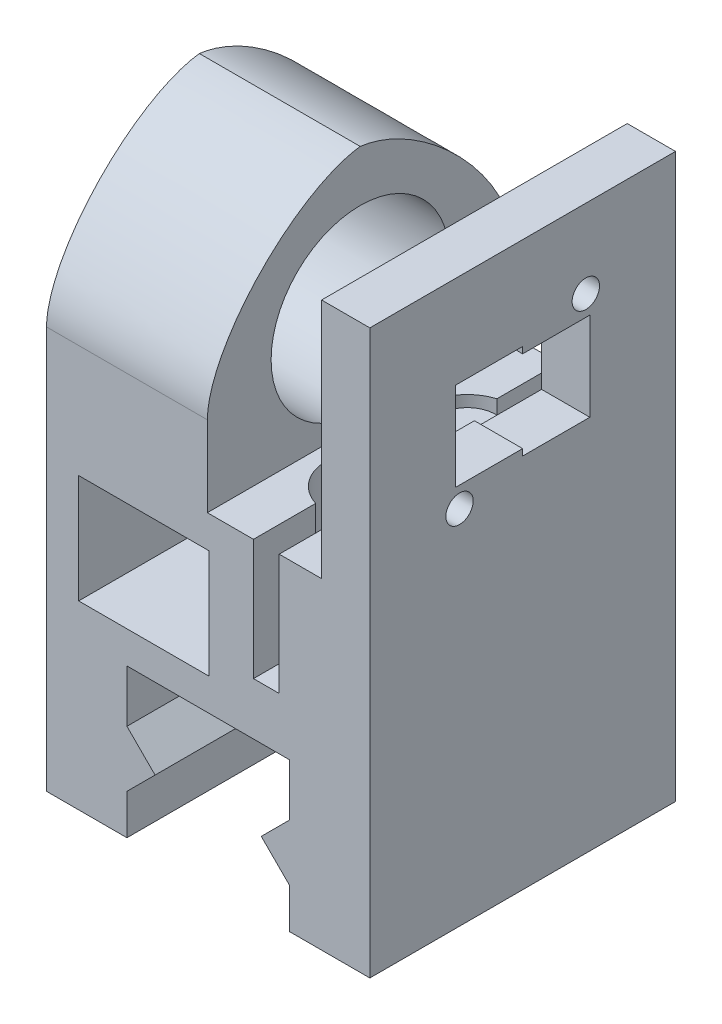
SolidWorks part; units mm, degrees
ref_plane "Front Plane" through (0, 0, 0) normal (0, 0, 1) x (1, 0, 0)
ref_plane "Top Plane" through (0, 0, 0) normal (0, 1, 0) x (1, 0, 0)
ref_plane "Right Plane" through (0, 0, 0) normal (1, 0, 0) x (0, 0, -1)
sketch "Sketch1" plane through (0, 0, 0) normal (0, 0, 1) x (1, 0, 0)
  line L0 (-10.1, 0) -> (10.1, 0)
  line L1 (10.1, 0) -> (10.1, -6.5)
  line L2 (10.1, -6.5) -> (6.6, -10)
  line L3 (6.6, -10) -> (10.1, -10) construction
  line L4 (10.1, -13.5) -> (6.6, -10)
  line L5 (10.1, -13.5) -> (10.1, -18.5)
  line L6 (0, 0) -> (0, -50000) construction
  line L7 (10.1, -18.5) -> (20.1, -18.5)
  line L8 (20.1, -18.5) -> (20.1, 21.5)
  line L9 (20.1, 21.5) -> (-20.1, 21.5)
  line L10 (-6.6, -10) -> (-10.1, -10) construction
  line L11 (-20.1, -18.5) -> (-20.1, 21.5)
  line L12 (-10.1, -18.5) -> (-20.1, -18.5)
  line L13 (-10.1, -13.5) -> (-10.1, -18.5)
  line L14 (-10.1, -13.5) -> (-6.6, -10)
  line L15 (-10.1, -6.5) -> (-6.6, -10)
  line L16 (-10.1, 0) -> (-10.1, -6.5)
  line L18 (-16.1, 17.5) -> (0.1, 17.5)
  line L19 (-16.1, 17.5) -> (-16.1, 4)
  line L20 (-16.1, 4) -> (0.1, 4)
  line L21 (0.1, 17.5) -> (0.1, 4)
  point P16 (0, 21.5)
  point P21 (0, 0)
  dimension "D1" = 10.1
  dimension "D2" = 6.5
  dimension "D3" = 3.5
  dimension "D4" = 45
  dimension "D5" = 5
  dimension "D6" = 10
  dimension "D7" = 40
  dimension "D8" = 4
  dimension "D9" = 4
  dimension "D10" = 20
  dimension "D11" = 4
extrude "Boss-Extrude1" add sketch "Sketch1" along normal mid plane 38
sketch "Sketch2" plane through (0, 21.5, 0) normal (0, 1, 0) x (1, 0, 0)
  line L0 (20.1, -19) -> (-20.1, -19) construction
  line L1 (-20.1, 19) -> (-0.1, 19)
  line L2 (-20.1, 19) -> (-20.1, -19)
  line L3 (-20.1, -19) -> (-0.1, -19)
  line L4 (-0.1, 19) -> (-0.1, -19)
  dimension "D1" = 20
extrude "Boss-Extrude2" add sketch "Sketch2" along normal blind 30
fillet "Fillet2" radius 20 2 edges at (-10.1, 51.5, -19) (-10.1, 51.5, 19) conic rho 0.3
sketch "Sketch7" plane through (0, 21.5, 0) normal (0, 1, 0) x (1, 0, 0)
  line L0 (20.1, 19) -> (-0.1, 19) construction
  line L1 (14.1, 19) -> (20.1, 19)
  line L2 (14.1, 19) -> (14.1, -19)
  line L3 (14.1, -19) -> (20.1, -19)
  line L4 (20.1, 19) -> (20.1, -19)
  dimension "D1" = 6
extrude "Boss-Extrude6" add sketch "Sketch7" along normal blind 30
sketch "Sketch3" plane through (-20.1, 0, 0) normal (-1, 0, 0) x (0, 0, 1)
  line L0 (0, 0) -> (0, 44) construction
  circle A0 centre (0, 34) radius 11.075
  dimension "D1" = 22.15
  dimension "D2" = 34
extrude "Cut-Extrude1" cut sketch "Sketch3" against normal blind 31 and the other way through all
sketch "Sketch9" plane through (20.1, 0, 0) normal (1, 0, 0) x (0, 0, -1)
  line L0 (-19, 51.5) -> (19, 51.5) construction
  line L1 (-19, -18.5) -> (-19, 51.5) construction
  line L4 (-11.6, 45.5) -> (11.6, 45.5) construction
  line L5 (-11.6, 45.5) -> (-11.6, 22.7) construction
  line L6 (-11.6, 22.7) -> (11.6, 22.7) construction
  line L7 (11.6, 45.5) -> (11.6, 22.7) construction
  circle A1 centre (7.85, 41.75) radius 2.2
  circle A2 centre (-7.85, 26.45) radius 2.2
  point P2 (7.85, 41.75)
  point P4 (-7.85, 26.45)
  dimension "D2" = 3.75
  dimension "D3" = 3.75
  dimension "D4" = 3.75
  dimension "D6" = 4.4
  dimension "D5" = 3.75
  dimension "D9" = 22.8
  dimension "D10" = 23.2
  dimension "D11" = 7.4
  dimension "D12" = 6
ref_axis "Axis1" through (-0.1, 34, 0) along (-1, 0, 0)
sketch "Sketch5" plane through (0, 21.5, 0) normal (0, 1, 0) x (1, 0, 0)
  line L0 (14.1, 19) -> (-0.1, 19) construction
  line L1 (17.6, 19) -> (20.1, 19)
  line L2 (17.6, 19) -> (17.6, -19)
  line L3 (17.6, -19) -> (20.1, -19)
  line L4 (20.1, 19) -> (20.1, -19)
  line L5 (14.1, -19) -> (-0.1, -19) construction
  line L6 (20.1, -19) -> (20.1, 19) construction
  dimension "D1" = 2.5
extrude "Boss-Extrude3" add sketch "Sketch5" along normal blind 30
sketch "Sketch11" plane through (0, 21.5, 0) normal (0, 1, 0) x (1, 0, 0)
  line L0 (-0.1, 0) -> (20.1, 0) construction
  line L1 (20.1, -19) -> (20.1, 19) construction
  line L2 (7.23, 19) -> (7.23, -19) construction
  line L3 (5.63, -11.2621) -> (5.63, -19)
  line L4 (8.83, -11.2621) -> (8.83, -19)
  line L5 (5.63, 19) -> (5.63, 11.2621)
  line L6 (8.83, 19) -> (8.83, 11.2621)
  line L7 (5.63, 19) -> (8.83, 19)
  line L8 (5.63, -19) -> (8.83, -19)
  line L11 (1.73, 6) -> (1.73, -6)
  line L12 (12.73, 6) -> (12.73, -6)
  line L13 (14.1, 19) -> (14.1, -19) construction
  circle A0 centre (7.23, 6) radius 3.5
  circle A1 centre (7.23, -6) radius 3.5
  arc A2 (12.73, 6) -> (8.83, 11.2621) centre (7.23, 6) ccw
  arc A3 (8.83, -11.2621) -> (12.73, -6) centre (7.23, -6) ccw
  arc A4 (1.73, -6) -> (5.63, -11.2621) centre (7.23, -6) ccw
  arc A5 (5.63, 11.2621) -> (1.73, 6) centre (7.23, 6) ccw
  dimension "D7" = 7
  dimension "D8" = 11
  dimension "D9" = 11
  dimension "D1" = 38
  dimension "D2" = 3.2
  dimension "D3" = 5.73
  dimension "D4" = 19
  dimension "D5" = 6
  dimension "D6" = 6
  dimension "D10" = 12
  dimension "D11" = 12
extrude "Cut-Extrude5" cut sketch "Sketch11" against normal blind 15
extrude "Boss-Extrude7" add sketch "Sketch9" against normal blind 8
sketch "Sketch19" plane through (20.1, 0, 0) normal (1, 0, 0) x (0, 0, -1)
  line L0 (-19, -18.5) -> (-19, 51.5) construction
  line L1 (-11.6, 45.5) -> (11.6, 45.5) construction
  line L2 (-11.6, 45.5) -> (-11.6, 22.7) construction
  line L3 (-11.6, 22.7) -> (11.6, 22.7) construction
  line L4 (11.6, 45.5) -> (11.6, 22.7) construction
  line L5 (-19, 51.5) -> (19, 51.5) construction
  line L7 (0, 39.2) -> (8.35, 39.2)
  line L8 (0, 29) -> (0, 28.2)
  line L9 (0, 28.2) -> (8.35, 28.2)
  line L10 (8.35, 39.2) -> (8.35, 28.2)
  line L11 (-8.35, 40) -> (0, 40)
  line L12 (-8.35, 40) -> (-8.35, 29)
  line L13 (-8.35, 29) -> (0, 29)
  line L14 (0, 40) -> (0, 39.2)
  dimension "D1" = 23.2
  dimension "D2" = 22.8
  dimension "D3" = 7.4
  dimension "D4" = 6
  dimension "D5" = 11
  dimension "D6" = 8.35
  dimension "D7" = 16.5
  dimension "D8" = 0.8
  dimension "D9" = 11
  dimension "D10" = 8.35
  dimension "D11" = 16.5
  dimension "D12" = 11.6
hole_wizard "M3 Clearance Hole3" positions "3DSketch3" profile "Sketch20" hole size "M3" standard "ANSI Metric"
sketch3d "3DSketch3"
  line L0 (12.1, 41.75, -7.85) -> (14.1, 41.75, -7.85) construction
  line L1 (12.1, 26.45, 7.85) -> (14.1, 26.45, 7.85) construction
  point P0 (12.1, 41.75, -7.85)
  point P4 (12.1, 26.45, 7.85)
sketch "Sketch20" plane through (12.1, 41.75, -7.85) normal (0, 1, 0) x (0, 0, 1)
  line L0 (0, 0) -> (0, 8)
  line L1 (0, 8) -> (1.7, 8)
  line L2 (1.7, 8) -> (1.7, 0)
  line L5 (1.7, 0) -> (0, 0)
  line L10 (0, 8) -> (-1.7, 8) construction
  line L11 (0, -6.35) -> (0, 107.95) construction
  dimension "Hole Dia." = 3.4
  dimension "Hole Depth" = 8
  dimension "Drill Angle" = 180
extrude "Cut-Extrude6" cut sketch "Sketch19" against normal blind 10
